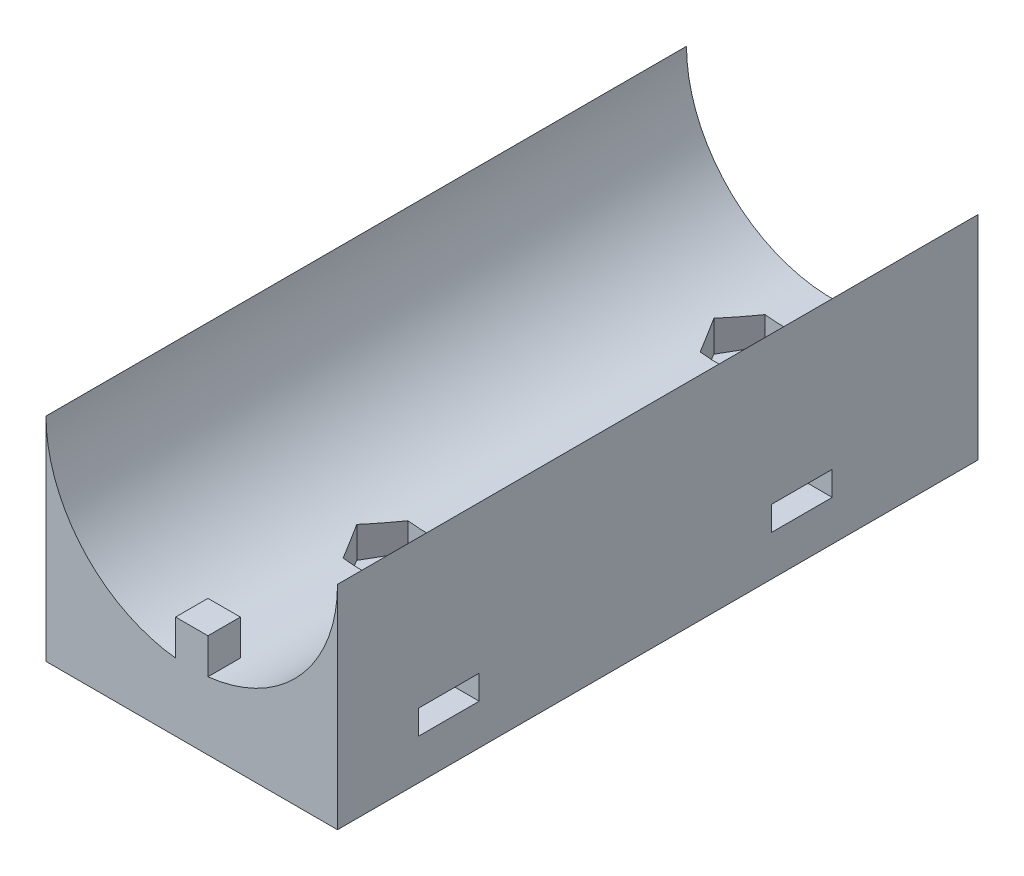
SolidWorks part; units mm, degrees
ref_plane "Plan de face" through (0, 0, 0) normal (0, 0, 1) x (1, 0, 0)
ref_plane "Plan de dessus" through (0, 0, 0) normal (0, 1, 0) x (1, 0, 0)
ref_plane "Plan de droite" through (0, 0, 0) normal (1, 0, 0) x (0, 0, -1)
sketch "Esquisse1" plane through (0, 0, 1608.5531) normal (0, 0, 1) x (1, 0, 0)
  line L0 (0, 17.4989) -> (36, 17.4989) construction
  line L1 (0, 0) -> (36, 0)
  line L2 (0, 26.25) -> (0, 0)
  line L6 (0, 26.25) -> (36, 26.25) construction
  line L8 (36, 26.25) -> (36, 0)
  arc A0 (0, 26.25) -> (36, 26.25) centre (18, 26.25) ccw
extrude "Boss.-Extru.1" add sketch "Esquisse1" along normal blind 79.1
sketch "Esquisse7" plane through (36, 0, 0) normal (1, 0, 0) x (0, 0, -1)
  line L0 (-1687.6531, 0) -> (-1608.5531, 0) construction
  line L1 (-1677.6531, 8) -> (-1670.1531, 8)
  line L2 (-1677.6531, 8) -> (-1677.6531, 5)
  line L3 (-1677.6531, 5) -> (-1670.1531, 5)
  line L4 (-1670.1531, 8) -> (-1670.1531, 5)
  line L5 (-1634.0531, 8) -> (-1626.5531, 8)
  line L6 (-1634.0531, 8) -> (-1634.0531, 5)
  line L7 (-1634.0531, 5) -> (-1626.5531, 5)
  line L8 (-1626.5531, 8) -> (-1626.5531, 5)
  line L10 (-1687.6531, 0) -> (-1687.6531, 26.25) construction
  line L11 (-1608.5531, 0) -> (-1608.5531, 26.25) construction
  dimension "D1" = 3
  dimension "D2" = 7.5
  dimension "D3" = 7.5
  dimension "D4" = 3
  dimension "D5" = 5
  dimension "D6" = 5
  dimension "D7" = 10
  dimension "D8" = 18
extrude "Boss.-Extru.3" add sketch "Esquisse7" along direction (-1, 0, 0) on the side against the normal up to surface (36 mm away) up to face at (0, 13.125, 1648.1031)
extrude "Enlèv. mat.-Extru.5" cut sketch "Esquisse7<2>" along direction (-1, 0, 0) on the side against the normal up to surface (36 mm away) up to face at (0, 13.125, 1648.1031)
sketch "Esquisse7<2>" plane through (36, 0, 0) normal (1, 0, 0) x (0, 0, -1) same geometry as "Esquisse7"
sketch "Esquisse9" plane through (0, 0, 0) normal (0, -1, 0) x (1, 0, 0)
  line L0 (20, 1683.6531) -> (20, 1687.6531)
  line L1 (20, 1683.6531) -> (16, 1683.6531)
  line L2 (20, 1687.6531) -> (16, 1687.6531)
  line L3 (16, 1683.6531) -> (16, 1687.6531)
  line L4 (20, 1683.6531) -> (16, 1687.6531) construction
  line L5 (20, 1687.6531) -> (16, 1683.6531) construction
  line L6 (0, 1687.6531) -> (0, 1608.5531) construction
  line L8 (0, 1687.6531) -> (36, 1687.6531) construction
  point P1 (18, 1685.6531)
  dimension "D1" = 4
  dimension "D2" = 4
  dimension "D3" = 16
  dimension "D4" = 0
extrude "Boss.-Extru.6" add sketch "Esquisse9" against normal blind 12.75
sketch "Esquisse11" plane through (0, 0, 0) normal (0, -1, 0) x (1, 0, 0)
  line L0 (0, 1608.5531) -> (36, 1608.5531) construction
  line L1 (0, 1687.6531) -> (36, 1687.6531) construction
  line L2 (0, 1687.6531) -> (0, 1608.5531) construction
  circle A0 centre (18, 1662.6531) radius 2.5
  circle A1 centre (18, 1618.5531) radius 2.5
  dimension "D3" = 18
  dimension "D1" = 10
  dimension "D2" = 25
  dimension "D4" = 18
extrude "Enlèv. mat.-Extru.6" cut sketch "Esquisse11" against normal blind 10
sketch "Esquisse12" plane through (0, 0, 0) normal (0, -1, 0) x (1, 0, 0)
  line L0 (0, 1687.6531) -> (36, 1687.6531) construction
  line L1 (20.3094, 1622.5531) -> (15.6906, 1622.5531)
  line L2 (15.6906, 1622.5531) -> (13.3812, 1618.5531)
  line L3 (13.3812, 1618.5531) -> (15.6906, 1614.5531)
  line L4 (15.6906, 1614.5531) -> (20.3094, 1614.5531)
  line L5 (20.3094, 1614.5531) -> (22.6188, 1618.5531)
  line L6 (22.6188, 1618.5531) -> (20.3094, 1622.5531)
  line L7 (20.3094, 1666.6531) -> (15.6906, 1666.6531)
  line L8 (15.6906, 1666.6531) -> (13.3812, 1662.6531)
  line L9 (13.3812, 1662.6531) -> (15.6906, 1658.6531)
  line L10 (15.6906, 1658.6531) -> (20.3094, 1658.6531)
  line L11 (20.3094, 1658.6531) -> (22.6188, 1662.6531)
  line L12 (22.6188, 1662.6531) -> (20.3094, 1666.6531)
  line L13 (0, 1608.5531) -> (36, 1608.5531) construction
  circle A0 centre (18, 1618.5531) radius 4 construction
  circle A1 centre (18, 1662.6531) radius 4 construction
  dimension "D1" = 8
  dimension "D2" = 8
  dimension "D3" = 0
  dimension "D4" = 0
extrude "Enlèv. mat.-Extru.12" cut sketch "Esquisse12" against normal blind 10 from offset 5 offset against normal yes
